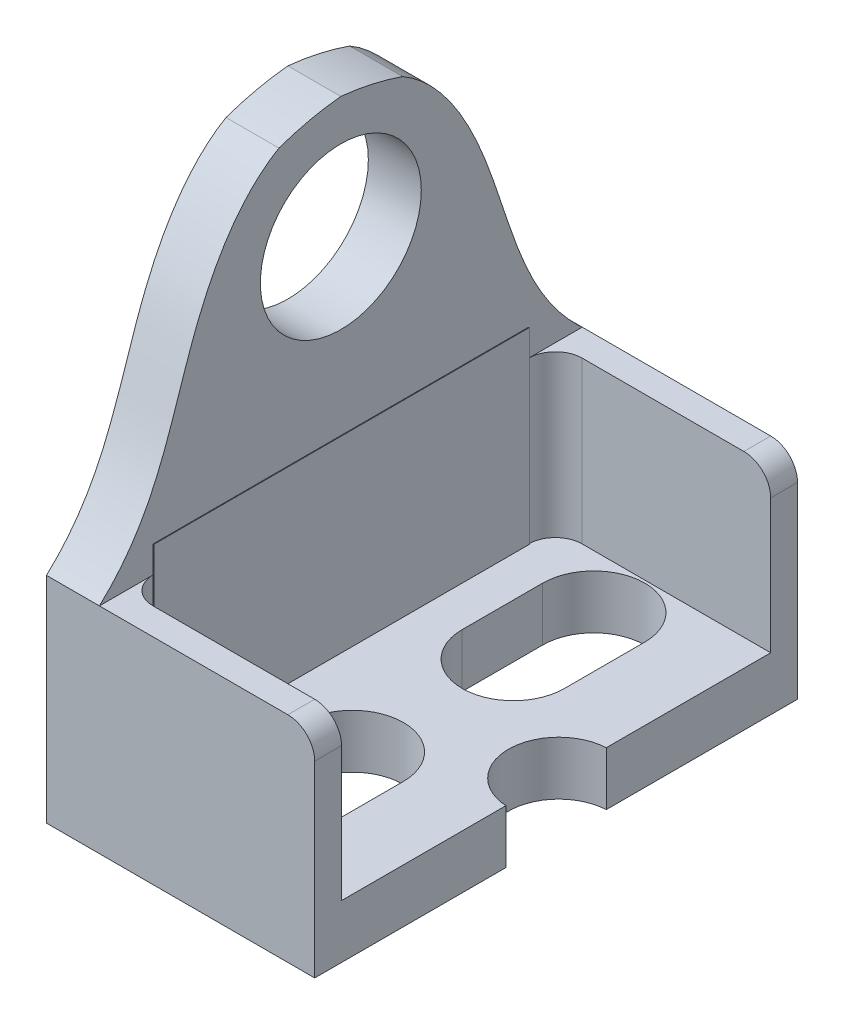
SolidWorks part; units mm, degrees
ref_plane "Alzado" through (0, 0, 0) normal (0, 0, 1) x (1, 0, 0)
ref_plane "Planta" through (0, 0, 0) normal (0, 1, 0) x (1, 0, 0)
ref_plane "Vista lateral" through (0, 0, 0) normal (1, 0, 0) x (0, 0, -1)
sketch "Croquis1" plane through (0, 0, 0) normal (0, 0, 1) x (1, 0, 0)
  line L0 (-15.0591, -60.6579) -> (84.9409, -60.6579)
  line L1 (84.9409, -60.6579) -> (84.9409, 29.3421)
  line L2 (84.9409, 29.3421) -> (4.6777, 29.3421)
  line L3 (4.6777, 29.3421) -> (4.6777, 139.3421)
  line L4 (4.6777, 139.3421) -> (-15.0591, 139.3421)
  line L5 (-15.0591, 139.3421) -> (-15.0591, -60.6579)
  dimension "D1" = 100
  dimension "D2" = 200
  dimension "D3" = 90
  dimension "D4" = 110
extrude "Saliente-Extruir1" add sketch "Croquis1" along normal blind 180
fillet "Redondeo1" radius 100 2 edges at (-5.1907, 139.3421, 180) (-5.1907, 139.3421, 0)
fillet "Redondeo2" radius 10 2 edges at (44.8093, 29.3421, 0) (44.8093, 29.3421, 180)
sketch "Croquis2" plane through (84.9409, 0, 0) normal (1, 0, 0) x (0, 0, -1)
  line L0 (-90, 138.8408) -> (-90, -74.1885) construction
  line L1 (-180, -60.6579) -> (-180, 19.3421) construction
  line L2 (-160, 29.3421) -> (-20, 29.3421)
  line L3 (-160, 29.3421) -> (-160, -40.6579)
  line L4 (-160, -40.6579) -> (-20, -40.6579)
  line L5 (-20, 29.3421) -> (-20, -40.6579)
  line L6 (0, -60.6579) -> (0, 19.3421) construction
  line L7 (-180, -60.6579) -> (0, -60.6579) construction
  line L10 (-170, 29.3421) -> (-10, 29.3421) construction
  point P9 (-180, -20.6579)
  dimension "D1" = 20
  dimension "D2" = 20
  dimension "D3" = 20
extrude "Cortar-Extruir4" cut sketch "Croquis2" along direction (-1, 0, 0) on the side against the normal blind 90
sketch "Croquis3" plane through (4.6777, 0, 0) normal (1, 0, 0) x (0, 0, -1)
  line L0 (-90, 138.8408) -> (-90, -81.0818) construction
  circle A0 centre (-90, 93.5486) radius 30
  dimension "D1" = 60
extrude "Cortar-Extruir5" cut sketch "Croquis3" against normal through all
sketch "Croquis4" plane through (0, -60.6579, 0) normal (0, -1, 0) x (-1, 0, 0)
  line L0 (-38.9755, -150) -> (-38.9755, -120) construction
  line L1 (-58.0102, -150) -> (-58.0102, -120)
  line L2 (-19.9409, -150) -> (-19.9409, -120)
  line L3 (-38.9755, -60) -> (-38.9755, -30) construction
  line L4 (-58.0102, -60) -> (-58.0102, -30)
  line L5 (-19.9409, -60) -> (-19.9409, -30)
  line L6 (15.0591, 0) -> (-84.9409, 0) construction
  line L7 (15.0591, -180) -> (-84.9409, -180) construction
  line L8 (15.0591, -180) -> (15.0591, 0) construction
  arc A0 (-58.0102, -150) -> (-19.9409, -150) centre (-38.9755, -150) ccw
  arc A1 (-19.9409, -120) -> (-58.0102, -120) centre (-38.9755, -120) ccw
  arc A2 (-58.0102, -60) -> (-19.9409, -60) centre (-38.9755, -60) ccw
  arc A3 (-19.9409, -30) -> (-58.0102, -30) centre (-38.9755, -30) ccw
  point P2 (-38.9755, -135)
  point P7 (-38.9755, -45)
  dimension "D3" = 30
  dimension "D1" = 30
  dimension "D2" = 30
  dimension "D4" = 30
  dimension "D5" = 35
  dimension "D6" = 35
extrude "Cortar-Extruir6" cut sketch "Croquis4" against normal through all
sketch "Croquis5" plane through (0, 29.3421, 0) normal (0, 1, 0) x (1, 0, 0)
  line L1 (4.6777, -10) -> (84.9409, -10)
  line L2 (4.6777, -10) -> (4.6777, -20)
  line L3 (4.6777, -20) -> (84.9409, -20)
  line L4 (84.9409, -10) -> (84.9409, -20)
  line L5 (4.6777, -160) -> (84.9409, -160)
  line L6 (4.6777, -160) -> (4.6777, -170)
  line L7 (4.6777, -170) -> (84.9409, -170)
  line L8 (84.9409, -160) -> (84.9409, -170)
extrude "Cortar-Extruir8" cut sketch "Croquis5" along direction (0, -1, 0) on the side against the normal blind 70
sketch "Croquis6" plane through (0, 0, 180) normal (0, 0, 1) x (1, 0, 0)
  line L1 (4.6777, 19.3421) -> (84.9409, 19.3421)
  line L2 (4.6777, 19.3421) -> (4.6777, 29.3421)
  line L3 (4.6777, 29.3421) -> (84.9409, 29.3421)
  line L4 (84.9409, 19.3421) -> (84.9409, 29.3421)
extrude "Cortar-Extruir9" cut sketch "Croquis6" against normal through all
fillet "Redondeo8" radius 10 2 edges at (84.9409, 19.3421, 175) (84.9409, 19.3421, 5)
sketch "Croquis7" plane through (4.6777, 0, 0) normal (1, 0, 0) x (0, 0, -1)
  line L0 (-90, 138.8408) -> (-90, -72.3502) construction
  arc A0 (-90, 138.8408) -> (-180, 39.3421) centre (-80, 39.3421) ccw construction
  arc A1 (0, 39.3421) -> (-90, 138.8408) centre (-100, 39.3421) ccw construction
  spline S0 degree 3 poles (-90, 138.8408) (-114.1373, 140.9485) (-151.8994, 94.8664) (-154.7545, 42.5253) (-180, 19.3421) knots 0 0 0 0 0.412965 1 1 1 1
  spline S1 degree 3 poles (-90, 138.8408) (-65.8627, 140.9485) (-28.1006, 94.8664) (-25.2455, 42.5253) (0, 19.3421) knots 0 0 0 0 0.412965 1 1 1 1
extrude "Cortar-Extruir10" cut sketch "Croquis7" against normal through all and the other way through all
sketch "Croquis8" plane through (-5.0591, 0, 0) normal (1, 0, 0) x (0, 0, -1)
  line L1 (-160, 29.3421) -> (-20, 29.3421)
  line L2 (-160, 29.3421) -> (-160, -40.6579)
  line L3 (-160, -40.6579) -> (-20, -40.6579)
  line L4 (-20, 29.3421) -> (-20, -40.6579)
extrude "Saliente-Extruir2" add sketch "Croquis8" along normal blind 10
sketch "Croquis9" plane through (0, -60.6579, 0) normal (0, -1, 0) x (1, 0, 0)
  line L0 (-15.0591, 90) -> (129.0568, 90) construction
  circle A0 centre (85.9241, 90) radius 18.7356
extrude "Cortar-Extruir11" cut sketch "Croquis9" against normal through all
fillet "Redondeo9" radius 10 2 edges at (4.6777, -10.6579, 170) (4.6777, -10.6579, 10)
sketch "Croquis19" plane through (4.6777, 0, 0) normal (1, 0, 0) x (0, 0, -1)
  circle A0 centre (-90, 93.5486) radius 30
sketch "Croquis33" plane through (-15.0591, 0, 0) normal (-1, 0, 0) x (0, 0, 1)
  circle A0 centre (90, 93.5486) radius 30
curve "Hélice/Espiral2" pitch 3.4167 height 20.5 turns 6
sketch "Croquis34" plane through (-15.0591, 0, 0) normal (-1, 0, 0) x (0, 0, 1)
  circle A0 centre (90, 93.5486) radius 30
  circle A1 centre (90, 93.5486) radius 30
